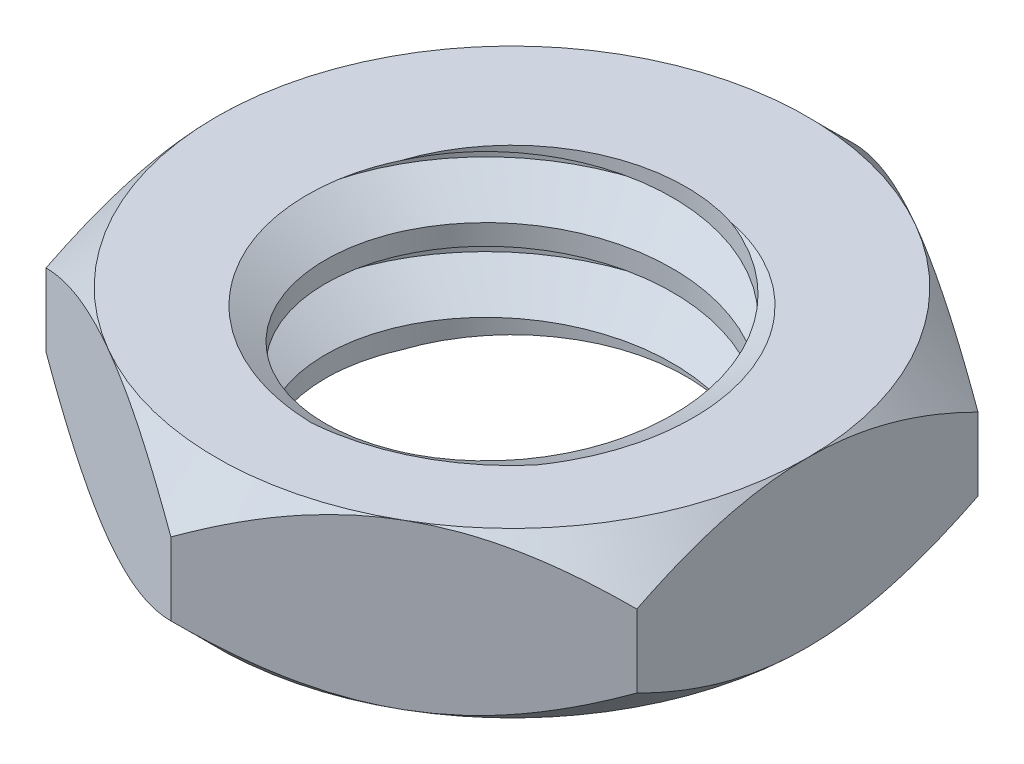
SolidWorks part; units mm, degrees
ref_plane "前视基准面" through (0, 0, 0) normal (0, 0, 1) x (1, 0, 0)
ref_plane "上视基准面" through (0, 0, 0) normal (0, 1, 0) x (1, 0, 0)
ref_plane "右视基准面" through (0, 0, 0) normal (1, 0, 0) x (0, 0, -1)
other "Configuration Table"
sketch "草图1" plane through (0, 0, 0) normal (0, 1, 0) x (1, 0, 0)
  line L1 (9, 5.1962) -> (0, 10.3923)
  line L2 (0, 10.3923) -> (-9, 5.1962)
  line L3 (-9, 5.1962) -> (-9, -5.1962)
  line L4 (-9, -5.1962) -> (0, -10.3923)
  line L5 (0, -10.3923) -> (9, -5.1962)
  line L6 (9, -5.1962) -> (9, 5.1962)
  circle A1 centre (0, 0) radius 9 construction
  circle A2 centre (0, 0) radius 5.3
  dimension "D1" = 10.6
  dimension "D2" = 18
extrude "凸台-拉伸1" add sketch "草图1" along normal blind 5 contours L3 L4 L5 L6 L1 L2
sketch "草图2" plane through (0, 5, 0) normal (0, 1, 0) x (1, 0, 0)
  line L0 (9, 5.1962) -> (0, 10.3923) construction
  circle A0 centre (0, 0) radius 9
extrude "切除-拉伸4" cut sketch "草图2" against normal blind 10 draft 45 flip side to cut
extrude "切除-拉伸5" cut sketch "草图2<2>" along normal blind 5 draft 45 from surface flip side to cut starting at face at (0, 0, 0)
sketch "草图2<2>" plane through (0, 5, 0) normal (0, 1, 0) x (1, 0, 0) same geometry as "草图2"
extrude "切除-拉伸6" cut sketch "草图1<5>" along normal through all contours A2
sketch "草图1<5>" plane through (0, 0, 0) normal (0, 1, 0) x (1, 0, 0) same geometry as "草图1"
thread "螺纹线1" pitch 2.5 method cut profile "螺纹线轮廓1" start angle 0, offset 3, length 0, pitch 2.5, diameter 10.6
ref_plane "基准面1" through (5.3, -3, 0) normal (0, 0, 1) x (1, 0, 0)
sketch "螺纹线轮廓1" plane through (5.3, -3, 0) normal (0, 0, 1) x (1, 0, 0)
  line L0 (0, 0) -> (0, 2.5) construction
  line L1 (0, 0) -> (1.3532, 0.7812)
  line L2 (1.3532, 0.7812) -> (1.3532, 1.0937)
  line L3 (1.3532, 1.0937) -> (0, 1.875)
  line L4 (1.3532, 0.9375) -> (0, 0.9375) construction
  line L11 (0, 0) -> (0, 1.875)
  point P2 (0, 0)
  dimension "Pitch" = 2.5
  dimension "Profile_Angle" = 60
  dimension "Profile_Land" = 0.3125
  dimension "Profile_Height" = 1.3532
